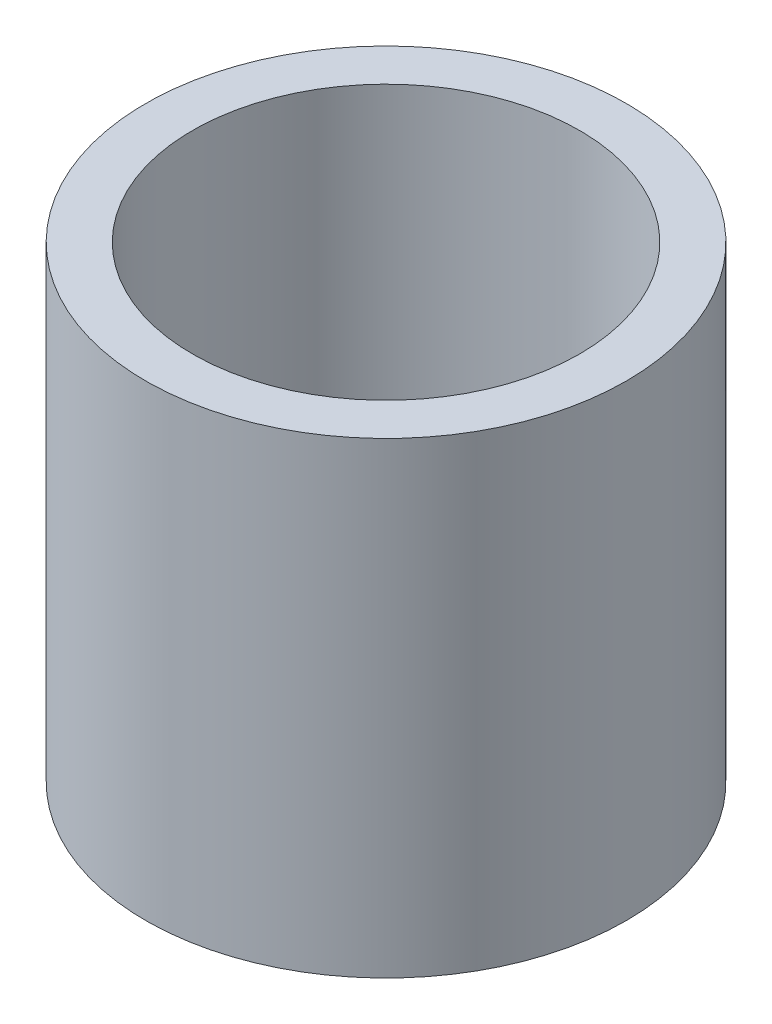
SolidWorks part; units mm, degrees
material "AISI 321 Annealed Stainless Steel (SS)"
ref_plane "Front Plane" through (0, 0, 0) normal (0, 0, 1) x (1, 0, 0)
ref_plane "Top Plane" through (0, 0, 0) normal (0, 1, 0) x (1, 0, 0)
ref_plane "Right Plane" through (0, 0, 0) normal (1, 0, 0) x (0, 0, -1)
sketch "Sketch1" plane through (0, 0, 0) normal (0, 0, 1) x (1, 0, 0)
  line L0 (0, -1459.8926) -> (0, 71534.7381) construction
  line L1 (16, -17.5) -> (16, -4.5)
  line L2 (16, -4.5) -> (14.5, -4.5)
  line L5 (14.5, -4.5) -> (14.5, 17.5)
  line L6 (14.5, 17.5) -> (18, 17.5)
  line L7 (18, 17.5) -> (18, -17.5)
  line L8 (18, -17.5) -> (16, -17.5)
  point P12 (18, 0)
  dimension "D1" = 35
  dimension "D2" = 36
  dimension "D3" = 32
  dimension "D4" = 22
  dimension "D5" = 29
revolve "Revolve1" add sketch "Sketch1" angle 360 about L0
